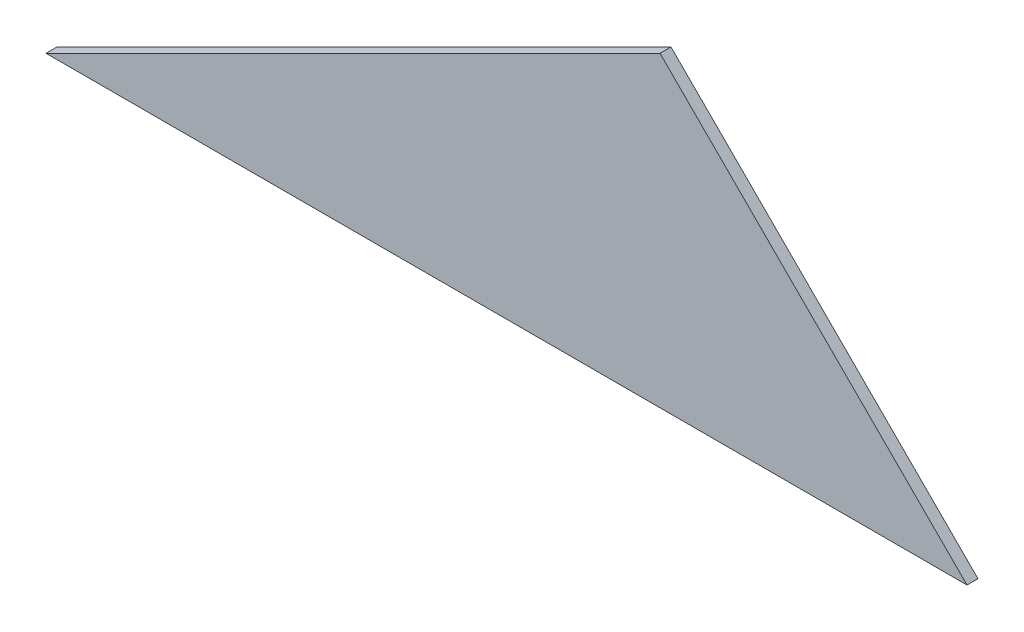
SolidWorks part; units mm, degrees
ref_plane "Front Plane" through (0, 0, 0) normal (0, 0, 1) x (1, 0, 0)
ref_plane "Top Plane" through (0, 0, 0) normal (0, 1, 0) x (1, 0, 0)
ref_plane "Right Plane" through (0, 0, 0) normal (1, 0, 0) x (0, 0, -1)
sketch "Sketch1" plane through (0, 0, 0) normal (0, 0, 1) x (1, 0, 0)
  line L0 (0, 0) -> (210, 0)
  line L1 (210, 0) -> (140, 70)
  line L2 (140, 70) -> (0, 0)
  dimension "D1" = 210
  dimension "D2" = 140
  dimension "D3" = 70
extrude "Boss-Extrude1" add sketch "Sketch1" along normal blind 2.5
ref_axis "Axis2" through (140, 70, 2.5) along (0, 0, -1)
ref_axis "Axis3" through (210, 0, 2.5) along (0, 0, -1)
